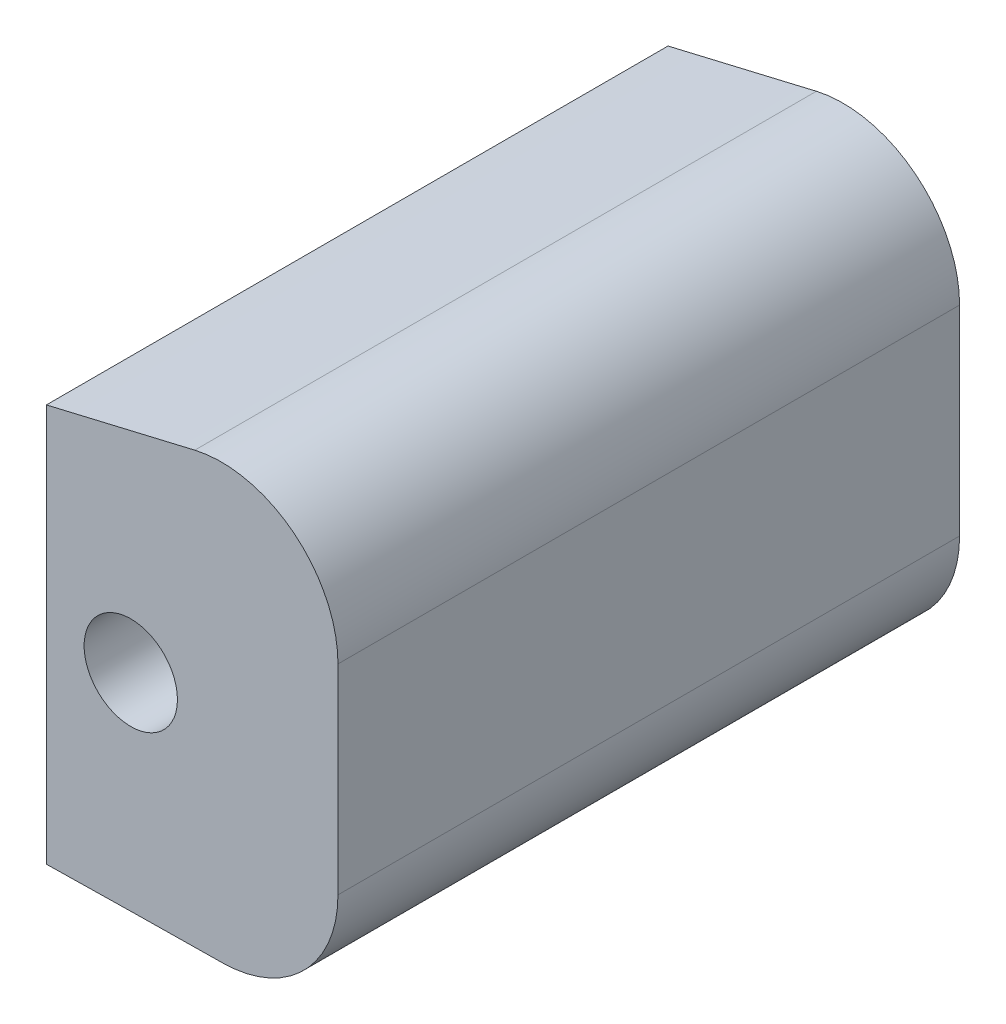
SolidWorks part; units mm, degrees
ref_plane "Front Plane" through (0, 0, 0) normal (0, 0, 1) x (1, 0, 0)
ref_plane "Top Plane" through (0, 0, 0) normal (0, 1, 0) x (1, 0, 0)
ref_plane "Right Plane" through (0, 0, 0) normal (1, 0, 0) x (0, 0, -1)
sketch "Sketch1" plane through (0, 0, 0) normal (0, 0, 1) x (1, 0, 0)
  line L0 (42.9183, -0.4477) -> (42.9183, 8.2631)
  circle A0 centre (-19.1025, -6.0109) radius 2.127
  circle A1 centre (12.6475, 4.4031) radius 2.127
  arc A2 (37.8951, -5.5274) -> (42.9183, -0.4477) centre (37.8383, -0.4477) ccw
  arc A3 (42.9183, 8.2631) -> (36.6811, 13.2095) centre (37.8383, 8.2631) ccw
  circle A4 centre (33.8935, 3.4217) radius 2.032
  spline S0 degree 3 poles (36.6811, 13.2095) (19.8298, 9.2672) (-2.0736, 3.8441) (-31.0965, -5.5459) (-39.3168, -8.8066) (-49.5156, -12.4957) (-45.7725, -12.1069) knots 0.118069 0.118069 0.118069 0.118069 0.630725 0.824214 0.940085 1 1 1 1
  spline S1 degree 3 poles (-45.7725, -12.1069) (-41.3374, -10.9993) (-33.8316, -10.53) (-20.4835, -8.7075) (-8.8734, -8.0192) (11.5246, -6.0282) (26.0673, -5.6598) (37.8951, -5.5274) knots 0 0 0 0 0.144322 0.237948 0.427123 0.512832 0.887818 0.887818 0.887818 0.887818
extrude "Boss-Extrude1" add sketch "Sketch1" along normal blind 27.0764
sketch "Sketch2" plane through (0, 0, 27.0764) normal (0, 0, 1) x (1, 0, 0)
  line L1 (-58.5048, 14.1188) -> (30.2183, 14.1188)
  line L2 (-58.5048, 14.1188) -> (-58.5048, -18.8296)
  line L3 (-58.5048, -18.8296) -> (30.2183, -18.8296)
  line L4 (30.2183, 14.1188) -> (30.2183, -18.8296)
  dimension "D1" = 12.7
extrude "Cut-Extrude1" cut sketch "Sketch2" against normal blind 27.0764
